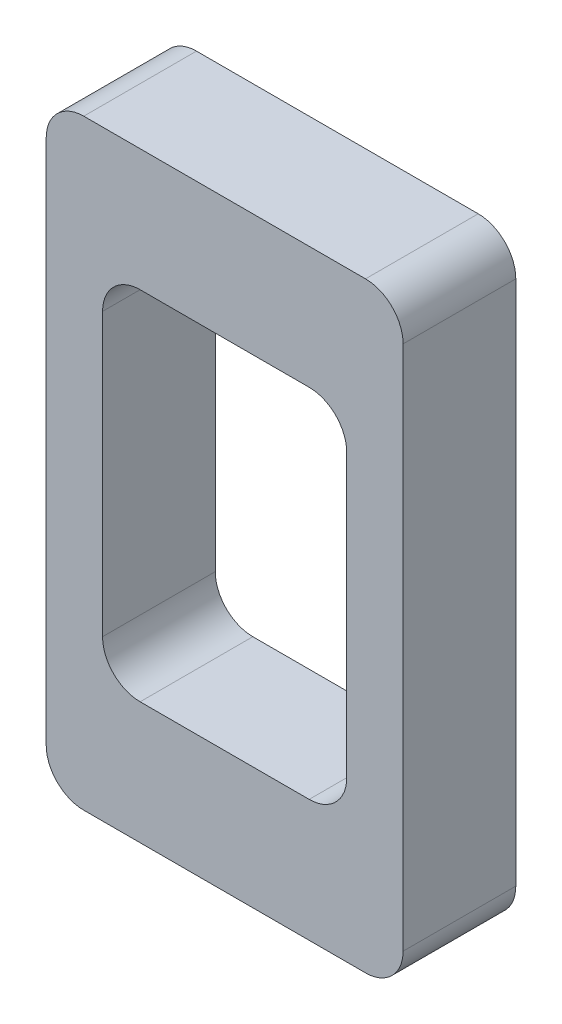
SolidWorks part; units mm, degrees
material "ABS"
ref_plane "Plan de face" through (0, 0, 0) normal (0, 0, 1) x (1, 0, 0)
ref_plane "Plan de dessus" through (0, 0, 0) normal (0, 1, 0) x (1, 0, 0)
ref_plane "Plan de droite" through (0, 0, 0) normal (1, 0, 0) x (0, 0, -1)
sketch "Esquisse1" plane through (0, 0, 0) normal (0, 0, 1) x (1, 0, 0)
  line L0 (-59.05, 42.3398) -> (-59.05, 32.8398)
  line L1 (-59.05, 42.3398) -> (-52.55, 42.3398)
  line L2 (-59.05, 32.8398) -> (-52.55, 32.8398)
  line L3 (-52.55, 42.3398) -> (-52.55, 32.8398)
  line L4 (-58.8, 45.5898) -> (-52.8, 45.5898) construction
  line L5 (-60.55, 45.5898) -> (-60.55, 29.5898)
  line L7 (-60.55, 45.5898) -> (-51.05, 45.5898)
  line L8 (-51.05, 45.5898) -> (-51.05, 29.5898)
  line L9 (-55.8, 42.8085) -> (-55.8, 34.5241) construction
  line L10 (-55.8, 29.5898) -> (-58.8, 29.5898) construction
  line L11 (-51.05, 29.5898) -> (-60.55, 29.5898)
  line L12 (-52.8, 44.5898) -> (-52.8, 40.5898) construction
  line L13 (-58.8, 30.5898) -> (-58.8, 44.5898) construction
  line L14 (-59.6005, 37.5898) -> (-50.0757, 37.5898) construction
  dimension "D2" = 9.5
  dimension "D1" = 6.5
  dimension "D3" = 9.5
extrude "Extrusion1" add sketch "Esquisse1" along normal blind 3
fillet "Congé1" radius 1 8 edges at (-60.55, 29.5898, 1.5) (-60.55, 45.5898, 1.5) (-51.05, 29.5898, 1.5) (-51.05, 45.5898, 1.5) (-52.55, 32.8398, 1.5) (-59.05, 32.8398, 1.5) (-59.05, 42.3398, 1.5) (-52.55, 42.3398, 1.5)
